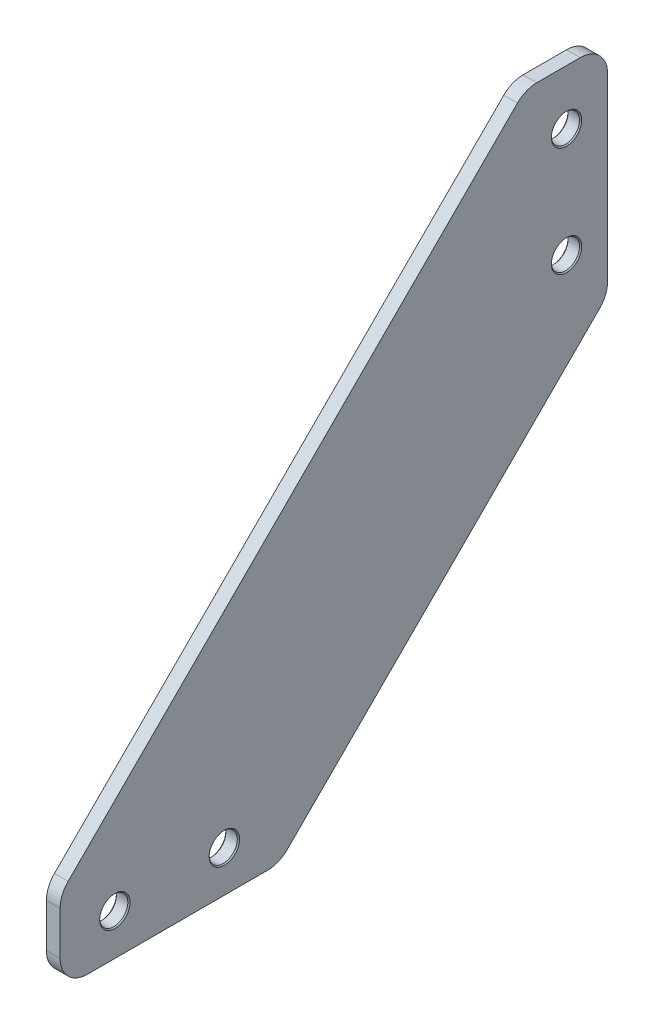
SolidWorks part; units mm, degrees
material "6061 Alloy"
ref_plane "Front Plane" through (0, 0, 0) normal (0, 0, 1) x (1, 0, 0)
ref_plane "Top Plane" through (0, 0, 0) normal (0, 1, 0) x (1, 0, 0)
ref_plane "Right Plane" through (0, 0, 0) normal (1, 0, 0) x (0, 0, -1)
sketch "Sketch1" plane through (0, 0, 0) normal (1, 0, 0) x (0, 0, -1)
  line L0 (0, 0) -> (0, 76.2) construction
  line L1 (0, 127) -> (-19.05, 127)
  line L2 (-19.05, 127) -> (-127, 19.05)
  line L3 (-127, 19.05) -> (-127, 0)
  line L4 (-127, 0) -> (-76.2, 0)
  line L5 (-76.2, 0) -> (0, 0) construction
  line L6 (0, 76.2) -> (0, 127)
  line L7 (-76.2, 0) -> (0, 76.2)
  line L8 (-127, 0) -> (0, 127) construction
  dimension "D1" = 45
  dimension "D2" = 127
  dimension "D3" = 19.05
  dimension "D4" = 50.8
extrude "1/8 in Sheet Metal" add sketch "Sketch1" along normal mid plane 3.175
ref_plane "Plane1" through (0, 9.525, 0) normal (0, -1, 0) x (-1, 0, 0)
ref_plane "Plane2" through (0, 0, 9.525) normal (0, 0, -1) x (-1, 0, 0)
ref_axis "Axis1" through (0, 9.525, 133.35) along (0, 0, -1)
ref_axis "Axis2" through (0, 72.375, 9.525) along (0, 1, 0)
hole_wizard "1/4 Clearance Hole1" positions "Sketch3" profile "Sketch4" hole size "1/4" standard "ANSI Inch" end condition through all
sketch "Sketch3" plane through (1.5875, 0, 0) normal (1, 0, 0) x (0, 0, -1)
  line L0 (-133.35, 9.525) -> (-74.9182, 9.525) construction
  line L1 (-9.525, 72.375) -> (-9.525, 133.35) construction
  line L2 (-127, 19.05) -> (-127, 0) construction
  line L3 (0, 127) -> (-19.05, 127) construction
  point P0 (-114.3, 9.525)
  point P4 (-88.9, 9.525)
  point P6 (-9.525, 88.9)
  point P10 (-9.525, 114.3)
  dimension "D1" = 25.4
  dimension "D2" = 25.4
  dimension "D3" = 12.7
  dimension "D4" = 12.7
sketch "Sketch4" plane through (1.5875, 9.525, 114.3) normal (0, 1, 0) x (0, 0, -1)
  line L0 (0, 0) -> (0, 3.175)
  line L1 (0, 3.175) -> (3.2639, 3.175)
  line L2 (3.2639, 3.175) -> (3.2639, 0)
  line L5 (3.2639, 0) -> (0, 0)
  line L11 (0, -6.35) -> (0, 107.95) construction
  dimension "Thru Hole Dia." = 6.5278
  dimension "Thru Hole Depth" = 3.175
fillet "Fillet 1/4 in" radius 6.35 6 edges at (0, 76.2, 0) (0, 127, 0) (0, 127, 19.05) (0, 19.05, 127) (0, 0, 76.2) (0, 0, 127)
chamfer "Chamfer 1/100 in" distance 0.254 angle 45 8 edges at (1.5875, 114.3, 6.2611) (-1.5875, 114.3, 6.2611) (1.5875, 88.9, 6.2611) (-1.5875, 88.9, 6.2611) (1.5875, 9.525, 111.0361) (-1.5875, 9.525, 111.0361) (1.5875, 9.525, 85.6361) (-1.5875, 9.525, 85.6361)
ref_plane "Center Plane" through (0, 0, 0) normal (0, -0.7071, 0.7071) x (1, 0, 0)
